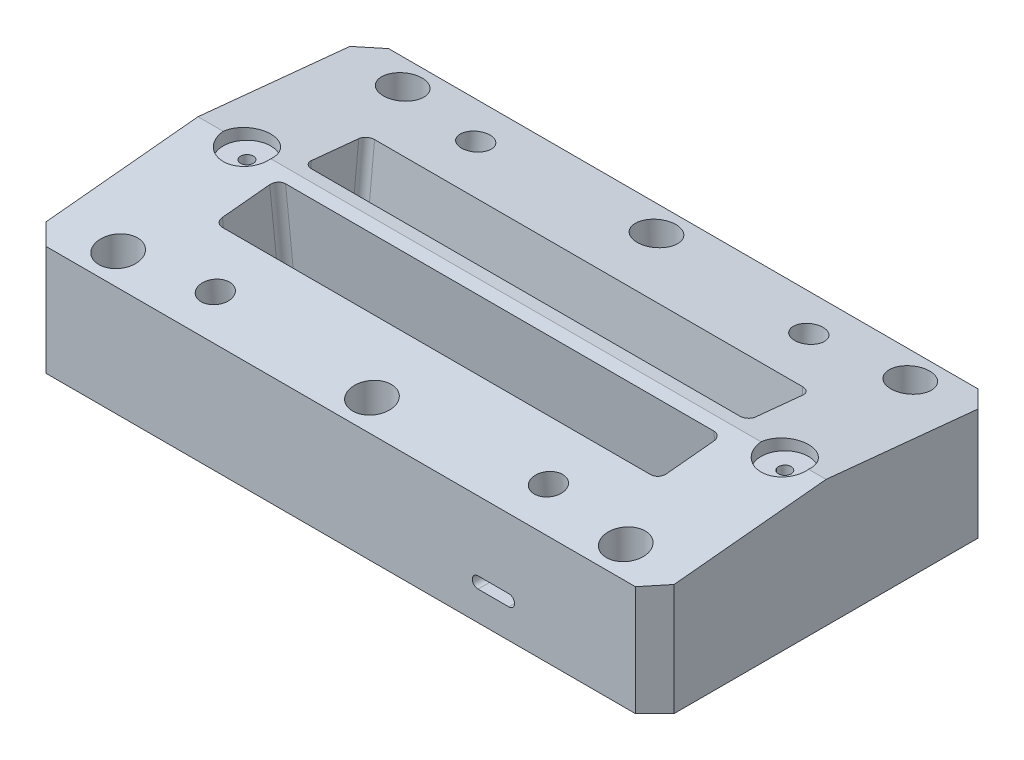
SolidWorks part; units mm, degrees
material "Custom Plastic"
ref_plane "Front Plane" through (0, 0, 0) normal (0, 0, 1) x (1, 0, 0)
ref_plane "Top Plane" through (0, 0, 0) normal (0, 1, 0) x (1, 0, 0)
ref_plane "Right Plane" through (0, 0, 0) normal (1, 0, 0) x (0, 0, -1)
sketch "Sketch1" plane through (0, 0, 0) normal (0, 1, 0) x (1, 0, 0)
  line L1 (0, 0) -> (198, 0)
  line L2 (0, 0) -> (0, 108)
  line L3 (0, 108) -> (198, 108)
  line L4 (198, 0) -> (198, 108)
  dimension "D1" = 198
  dimension "D2" = 108
extrude "Boss-Extrude1" add sketch "Sketch1" along normal blind 40
ref_plane "Left" through (198, 0, 0) normal (1, 0, 0) x (0, 0, -1)
ref_plane "Bot" through (0, 40, 0) normal (0, 1, 0) x (1, 0, 0)
ref_plane "der loco" through (0, 0, -52) normal (0, 0, -1) x (-1, 0, 0)
sketch "Sketch4" plane through (0, 0, 0) normal (0, 1, 0) x (1, 0, 0)
  line L0 (0, 108) -> (0, 0) construction
  line L1 (8.5, 31.5) -> (189.5, 31.5)
  line L2 (8.5, 31.5) -> (8.5, 76.5)
  line L3 (8.5, 76.5) -> (189.5, 76.5)
  line L4 (189.5, 31.5) -> (189.5, 76.5)
  line L5 (0, 0) -> (198, 0) construction
  dimension "D1" = 181
  dimension "D2" = 8.5
  dimension "D3" = 45
  dimension "D4" = 31.5
extrude "Cut-Extrude2" cut sketch "Sketch4" along normal blind 10 contours L2 L1 L4 L3
ref_plane "Plane32" through (0, 10, 0) normal (0, -1, 0) x (-1, 0, 0)
sketch "Sketch5" plane through (198, 0, 0) normal (1, 0, 0) x (0, 0, -1)
  line L0 (54, 40) -> (108, 34.6577)
  line L1 (0, 40) -> (108, 40) construction
  line L2 (108, 34.6577) -> (108, 40)
  line L3 (108, 40) -> (54, 40)
  line L4 (108, 40) -> (108, 0) construction
  dimension "D1" = 5.65
  dimension "D2" = 54
extrude "Cut-Extrude3" cut sketch "Sketch5" against normal up to vertex (198 mm away) up to point (0, 40, 0)
ref_plane "Plane24" through (0, 10, 0) normal (0, -1, 0) x (-1, 0, 0)
sketch "Sketch53" plane through (0, 10, 0) normal (0, -1, 0) x (-1, 0, 0)
  line L0 (-8.5, 51.5) -> (-8.5, 31.5)
  line L1 (-8.5, 76.5) -> (-8.5, 31.5) construction
  line L2 (-8.5, 31.5) -> (-39.5, 31.5)
  line L3 (-8.5, 31.5) -> (-189.5, 31.5) construction
  line L4 (-39.5, 31.5) -> (-8.5, 51.5)
  line L5 (-8.5, 54) -> (-189.5, 54) construction
  line L6 (-189.5, 31.5) -> (-189.5, 76.5) construction
  line L7 (-8.5, 56.5) -> (-8.5, 76.5)
  line L8 (-8.5, 76.5) -> (-39.5, 76.5)
  line L9 (-39.5, 76.5) -> (-8.5, 56.5)
  line L10 (-99, 76.5) -> (-99, 31.5) construction
  line L11 (-8.5, 76.5) -> (-189.5, 76.5) construction
  line L12 (-8.5, 31.5) -> (-189.5, 31.5) construction
  line L13 (-158.5, 76.5) -> (-189.5, 56.5)
  line L14 (-189.5, 76.5) -> (-158.5, 76.5)
  line L15 (-189.5, 56.5) -> (-189.5, 76.5)
  line L16 (-158.5, 31.5) -> (-189.5, 51.5)
  line L17 (-189.5, 31.5) -> (-158.5, 31.5)
  line L18 (-189.5, 51.5) -> (-189.5, 31.5)
  dimension "D1" = 31
  dimension "D2" = 20
extrude "Boss-Extrude11" add sketch "Sketch53" along normal up to surface (10 mm away) up to face at (99, 0, -54)
ref_plane "izq loco" through (0, 0, -57) normal (0, 0, -1) x (-1, 0, 0)
sketch "Sketch18" plane through (198, 0, 0) normal (1, 0, 0) x (0, 0, -1)
  line L0 (0, 34.6577) -> (0, 40)
  line L1 (0, 40) -> (0, 0) construction
  line L2 (0, 40) -> (54, 40)
  line L3 (54, 40) -> (0, 34.6577)
  line L4 (0, 40) -> (54, 40) construction
  dimension "D1" = 54
  dimension "D2" = 5.65
extrude "Cut-Extrude12" cut sketch "Sketch18" against normal up to surface (198 mm away) up to face at (0, 22.9315, -54)
sketch "Sketch60" plane through (0, 0, 0) normal (0, 1, 0) x (1, 0, 0)
  point P0 (8.5, 31.5)
  point P1 (39.5, 31.5)
  point P2 (8.5, 76.5)
  point P6 (39.5, 76.5)
  dimension "D1" = 20
  dimension "D2" = 31
  dimension "D3" = 20
  dimension "D4" = 31
ref_axis "Axis6" through (8.5, 0, -31.5) along (1, 0, 0)
sketch "Sketch69" plane through (0, 10, 0) normal (0, -1, 0) x (-1, 0, 0)
  point P0 (-39.5, 56.5)
  point P1 (-8.5, 51.5)
  point P2 (-38.5, 51.5)
  point P3 (-8.5, 56.5)
  dimension "D1" = 31
  dimension "D2" = 20
  dimension "D3" = 20
  dimension "D4" = 30
sketch "der loco axis" plane through (0, 0, -52) normal (0, 0, -1) x (-1, 0, 0)
  point P0 (-8.5, 8.5)
  point P1 (-38.5, 8.5)
  dimension "D1" = 1.5
sketch "izq loco axis" plane through (0, 0, -57) normal (0, 0, -1) x (-1, 0, 0)
  line L0 (-39.5, 0) -> (-39.5, 10) construction
  line L1 (-8.5, 0) -> (-8.5, 10) construction
  point P0 (-8.5, 8.4959)
  point P1 (-39.5, 8.4959)
  dimension "D1" = 1.5041
ref_plane "Plane3" through (0, 44.9028, -4.4423) normal (0, 0.9951, -0.0985) x (1, 0, 0)
ref_axis "Axis8" through (39.5, 0, -76.5) along (-1, 0, 0)
ref_axis "Axis9" through (8.5, 8.4959, -57) along (1, 0, 0)
ref_axis "Axis10" through (38.5, 8.5, -52) along (-1, 0, 0)
ref_plane "Izq bueno" through (0, 28.0127, -12.2048) normal (0, 0.9168, -0.3994) x (1, 0, 0)
sketch "Izq" plane through (0, 28.0127, -12.2048) normal (0, 0.9168, -0.3994) x (1, 0, 0)
  line L0 (8.5, 48.8622) -> (29.5, 70.1326)
  line L1 (29.5, 70.1326) -> (8.5, 70.1326)
  line L2 (8.5, 70.1326) -> (8.5, 48.8622)
  dimension "D1" = 21
extrude "Cut-Extrude28" cut sketch "Izq" against normal blind 14.5
ref_plane "Der bueno" through (0, -11.1449, -4.6211) normal (0, 0.9237, 0.383) x (1, 0, 0)
sketch "Der" plane through (0, -11.1449, -4.6211) normal (0, 0.9237, 0.383) x (1, 0, 0)
  line L0 (8.5, 51.2902) -> (29.5, 29.0979)
  line L1 (29.5, 29.0979) -> (8.5, 29.0979)
  line L2 (8.5, 29.0979) -> (8.5, 51.2902)
  dimension "D1" = 21
extrude "Cut-Extrude29" cut sketch "Der" against normal blind 14.5
sketch "Sketch97" plane through (0, 0, 0) normal (0, 1, 0) x (1, 0, 0)
  line L0 (8.5, 57.5) -> (29.5, 76.5)
  line L1 (29.5, 76.5) -> (158.5, 76.5)
  line L3 (158.5, 31.5) -> (29.5, 31.5)
  line L4 (29.5, 31.5) -> (8.5, 51.5)
  line L5 (8.5, 51.5) -> (8.5, 57.5)
  line L7 (158.5, 76.5) -> (189.5, 56.5)
  line L8 (189.5, 56.5) -> (189.5, 51.5)
  line L9 (189.5, 51.5) -> (158.5, 31.5)
  line L10 (39.5, 76.5) -> (158.5, 76.5) construction
  dimension "D1" = 6
extrude "Cut-Extrude40" cut sketch "Sketch97" along normal up to surface (10 mm away) up to face at (99, 10, -54)
ref_axis "Axis11" through (99, 0, -108) along (0, 0, 1)
ref_plane "Plane33" through (99, 0, 0) normal (1, 0, 0) x (0, 0, -1)
mirror "Mirror2" about plane through (99, 0, 0) normal (1, 0, 0) of "Cut-Extrude29", "Cut-Extrude40", "Cut-Extrude28"
sketch "Sketch6" plane through (0, 44.9028, -4.4423) normal (0, 0.9951, -0.0985) x (1, 0, 0)
  line L0 (0, 49.7996) -> (198, 49.7996) construction
  line L1 (28.9, 77.1996) -> (169.5, 77.1996)
  line L2 (25.9, 74.1996) -> (25.9, 53.5996)
  line L3 (28.9, 50.5996) -> (169.5, 50.5996)
  line L4 (172.5, 74.1996) -> (172.5, 53.5996)
  line L7 (28.6, 53.2996) -> (169.8, 53.2996)
  line L8 (28.6, 53.2996) -> (28.6, 74.4996)
  line L9 (28.6, 74.4996) -> (169.8, 74.4996)
  line L10 (169.8, 53.2996) -> (169.8, 74.4996)
  line L13 (198, 49.7996) -> (198, 104.0632) construction
  arc A0 (169.5, 77.1996) -> (172.5, 74.1996) centre (169.5, 74.1996) cw
  arc A1 (169.5, 50.5996) -> (172.5, 53.5996) centre (169.5, 53.5996) ccw
  arc A2 (25.9, 53.5996) -> (28.9, 50.5996) centre (28.9, 53.5996) ccw
  arc A3 (28.9, 77.1996) -> (25.9, 74.1996) centre (28.9, 74.1996) ccw
  dimension "D1" = 3
  dimension "D2" = 146.6
  dimension "D3" = 20.6
  dimension "D4" = 25.5
  dimension "D5" = 3.5
  dimension "D6" = 2.7
  dimension "D7" = 2.7
  dimension "D8" = 2.7
  dimension "D9" = 2.7
sketch "Sketch9" plane through (0, 40, 0) normal (0, 1, 0) x (1, 0, 0)
  line L1 (0, 54) -> (198, 54) construction
  circle A0 centre (15.45, 54) radius 8
  point P2 (0, 0)
  point P3 (15.45, 54)
  dimension "D1" = 16
  dimension "D2" = 15.45
sketch "Sketch12" plane through (0, 40, 0) normal (0, 1, 0) x (1, 0, 0)
  line L1 (0, 108) -> (198, 108) construction
  line L4 (0, 0) -> (198, 0) construction
  circle A0 centre (19.7, 98.85) radius 3.15
  circle A1 centre (99.7, 9.15) radius 3.15
  circle A2 centre (179.7, 9.15) radius 3.15
  circle A3 centre (19.7, 9.15) radius 3.15
  circle A4 centre (99.7, 98.85) radius 3.15
  circle A5 centre (179.7, 98.85) radius 3.15
  dimension "D1" = 9.15
  dimension "D2" = 6.3
  dimension "D3" = 9.15
  dimension "D4" = 19.7
  dimension "D7" = 80
  dimension "D9" = 80
extrude "Cut-Extrude9" cut sketch "Sketch12" against normal through all
sketch "Sketch13" plane through (0, 44.9028, -4.4423) normal (0, 0.9951, -0.0985) x (1, 0, 0)
  line L1 (0, 104.0632) -> (198, 104.0632) construction
  line L2 (198, 49.7996) -> (198, 104.0632) construction
  line L3 (0, 49.7996) -> (0, 104.0632) construction
  circle A0 centre (46.5, 91.0632) radius 4.5
  circle A1 centre (151.5, 91.0632) radius 4.5
  dimension "D1" = 9
  dimension "D4" = 9
  dimension "D2" = 46.5
  dimension "D3" = 13
  dimension "D5" = 46.5
extrude "Cut-Extrude10" cut sketch "Sketch13" against normal blind 16.5
sketch "Sketch14" plane through (0, 34.0326, 6.3177) normal (0, 0.9951, 0.0985) x (1, 0, 0)
  line L3 (198, 6.3486) -> (198, 60.6122) construction
  line L4 (0, 60.6122) -> (198, 60.6122) construction
  circle A0 centre (46.5, 19.3937) radius 4.5
  circle A1 centre (151.5, 19.3937) radius 4.5
  dimension "D1" = 9
  dimension "D2" = 9
  dimension "D3" = 46.5
  dimension "D4" = 41.2185
  dimension "D5" = 46.5
extrude "Cut-Extrude11" cut sketch "Sketch14" against normal blind 16.5
ref_plane "Plane9" through (0, 34.3217, 3.3955) normal (0, 0.9951, 0.0985) x (1, 0, 0)
sketch "Sketch23" plane through (0, 34.3217, 3.3955) normal (0, 0.9951, 0.0985) x (1, 0, 0)
  line L0 (0, 57.6757) -> (198, 57.6757) construction
  line L1 (28.9, 56.8757) -> (169.5, 56.8757)
  line L2 (25.9, 53.8757) -> (25.9, 33.2757)
  line L3 (28.9, 30.2757) -> (169.5, 30.2757)
  line L4 (172.5, 53.8757) -> (172.5, 33.2757)
  line L7 (28.6, 54.1757) -> (169.8, 54.1757)
  line L8 (28.6, 54.1757) -> (28.6, 32.9757)
  line L9 (28.6, 32.9757) -> (169.8, 32.9757)
  line L10 (169.8, 54.1757) -> (169.8, 32.9757)
  line L12 (198, 3.4121) -> (198, 57.6757) construction
  arc A0 (169.5, 56.8757) -> (172.5, 53.8757) centre (169.5, 53.8757) cw
  arc A1 (169.5, 30.2757) -> (172.5, 33.2757) centre (169.5, 33.2757) ccw
  arc A2 (25.9, 33.2757) -> (28.9, 30.2757) centre (28.9, 33.2757) ccw
  arc A3 (28.9, 56.8757) -> (25.9, 53.8757) centre (28.9, 53.8757) ccw
  point P10 (172.5, 56.8757)
  point P15 (25.9, 30.2757)
  point P18 (25.9, 56.8757)
  dimension "D5" = 3
  dimension "D1" = 146.6
  dimension "D2" = 20.6
  dimension "D3" = 3.5
  dimension "D4" = 25.5
  dimension "D6" = 2.7
  dimension "D7" = 2.7
  dimension "D8" = 2.7
  dimension "D9" = 2.7
sketch "Sketch41" plane through (0, 0, 0) normal (0, 1, 0) x (1, 0, 0)
  line L0 (198, 0) -> (198, 108) construction
  line L1 (198, 108) -> (0, 108) construction
  line L2 (0, 0) -> (198, 0) construction
  circle A0 centre (139.5, 9) radius 2.9
  circle A1 centre (139.5, 99) radius 2.9
  dimension "D1" = 5.8
  dimension "D4" = 5.8
  dimension "D2" = 58.5
  dimension "D3" = 58.5
  dimension "D5" = 9
  dimension "D6" = 9
extrude "Cut-Extrude21" cut sketch "Sketch41" along normal blind 7
sketch "Sketch42" plane through (0, 0, 0) normal (0, 0, 1) x (1, 0, 0)
  line L0 (198, 34.6577) -> (198, 0) construction
  line L5 (0, 0) -> (198, 0) construction
  line L6 (142.3, 12.8) -> (152, 12.8)
  line L7 (142.3, 9.2) -> (152, 9.2)
  arc A0 (142.3, 12.8) -> (142.3, 9.2) centre (142.3, 11) ccw
  arc A2 (152, 12.8) -> (152, 9.2) centre (152, 11) cw
  dimension "D2" = 1.8
  dimension "D3" = 1.8
  dimension "D1" = 9.7
  dimension "D5" = 46
  dimension "D6" = 11
extrude "Cut-Extrude22" cut sketch "Sketch42" against normal blind 10
ref_plane "Plane19" through (0, 0, -108) normal (0, 0, -1) x (-1, 0, 0)
sketch "Sketch43" plane through (0, 0, -108) normal (0, 0, -1) x (-1, 0, 0)
  line L0 (-55.7, 11) -> (-46, 11) construction
  line L1 (-55.7, 12.8) -> (-46, 12.8)
  line L2 (-55.7, 9.2) -> (-46, 9.2)
  line L3 (-198, 0) -> (0, 0) construction
  line L4 (0, 34.6577) -> (0, 0) construction
  arc A0 (-55.7, 12.8) -> (-55.7, 9.2) centre (-55.7, 11) ccw
  arc A1 (-46, 9.2) -> (-46, 12.8) centre (-46, 11) ccw
  point P2 (-50.85, 11)
  dimension "D2" = 1.8
  dimension "D1" = 9.7
  dimension "D3" = 11
  dimension "D4" = 46
extrude "Cut-Extrude23" cut sketch "Sketch43" against normal blind 10
sketch "Sketch84" plane through (0, 44.9028, -4.4423) normal (0, 0.9951, -0.0985) x (1, 0, 0)
  line L0 (0, 49.7996) -> (198, 49.7996) construction
  line L1 (31.7, 53.8996) -> (166.7, 53.8996)
  line L2 (29.2, 56.3996) -> (29.2, 71.3996)
  line L3 (31.7, 73.8996) -> (166.7, 73.8996)
  line L4 (169.2, 56.3996) -> (169.2, 71.3996)
  line L7 (0, 49.7996) -> (0, 104.0632) construction
  arc A0 (166.7, 53.8996) -> (169.2, 56.3996) centre (166.7, 56.3996) ccw
  arc A1 (166.7, 73.8996) -> (169.2, 71.3996) centre (166.7, 71.3996) cw
  arc A2 (29.2, 71.3996) -> (31.7, 73.8996) centre (31.7, 71.3996) cw
  arc A3 (31.7, 53.8996) -> (29.2, 56.3996) centre (31.7, 56.3996) cw
  point P10 (169.2, 53.8996)
  point P13 (169.2, 73.8996)
  point P16 (29.2, 73.8996)
  point P19 (169.2, 63.8996)
  dimension "D5" = 2.5
  dimension "D1" = 140
  dimension "D2" = 20
  dimension "D3" = 4.1
  dimension "D4" = 29.2
extrude "Cut-Extrude35" cut sketch "Sketch84" against normal blind 55.4
sketch "Sketch83" plane through (0, 34.3217, 3.3955) normal (0, 0.9951, 0.0985) x (1, 0, 0)
  line L1 (31.7, 53.5757) -> (166.7, 53.5757)
  line L2 (29.2, 51.0757) -> (29.2, 36.0757)
  line L3 (31.7, 33.5757) -> (166.7, 33.5757)
  line L4 (169.2, 51.0757) -> (169.2, 36.0757)
  line L7 (0, 57.6757) -> (198, 57.6757) construction
  line L8 (0, 57.6757) -> (0, 3.4121) construction
  arc A0 (166.7, 33.5757) -> (169.2, 36.0757) centre (166.7, 36.0757) ccw
  arc A1 (166.7, 53.5757) -> (169.2, 51.0757) centre (166.7, 51.0757) cw
  arc A2 (29.2, 36.0757) -> (31.7, 33.5757) centre (31.7, 36.0757) ccw
  arc A3 (31.7, 53.5757) -> (29.2, 51.0757) centre (31.7, 51.0757) ccw
  point P12 (169.2, 53.5757)
  point P15 (29.2, 33.5757)
  point P18 (29.2, 53.5757)
  point P19 (169.2, 43.5757)
  dimension "D5" = 2.5
  dimension "D1" = 140
  dimension "D2" = 20
  dimension "D3" = 29.2
  dimension "D4" = 4.1
extrude "Cut-Extrude34" cut sketch "Sketch83" against normal blind 55.4
sketch "Sketch85" plane through (0, 40, 0) normal (0, 1, 0) x (1, 0, 0)
  line L0 (0, 101.9) -> (6.1, 108)
  line L3 (6.1, 108) -> (0, 108)
  line L4 (0, 108) -> (0, 101.9)
  line L5 (0, 0) -> (6.1, 0)
  line L7 (6.1, 0) -> (0, 6.1)
  line L9 (0, 6.1) -> (0, 0)
  line L10 (198, 6.1) -> (191.9, 0)
  line L11 (198, 0) -> (198, 54) construction
  line L12 (0, 0) -> (198, 0) construction
  line L13 (191.9, 0) -> (198, 0)
  line L14 (198, 0) -> (198, 6.1)
  line L15 (198, 108) -> (191.9, 108)
  line L16 (0, 108) -> (198, 108) construction
  line L17 (191.9, 108) -> (198, 101.9)
  line L18 (198, 54) -> (198, 108) construction
  line L19 (198, 101.9) -> (198, 108)
  line L20 (0, 54) -> (0, 108) construction
  line L21 (0, 108) -> (198, 108) construction
  line L22 (0, 0) -> (198, 0) construction
  line L23 (0, 54) -> (0, 0) construction
  point P2 (0, 0)
  point P3 (0, 0)
  point P4 (0, 0)
  point P15 (0, 0)
  point P28 (0, 0)
  point P36 (0, 0)
  dimension "D1" = 6.1
  dimension "D2" = 6.1
  dimension "D3" = 6.1
  dimension "D4" = 6.1
  dimension "D5" = 6.1
  dimension "D6" = 6.1
  dimension "D7" = 6.1
extrude "Cut-Extrude36" cut sketch "Sketch85" against normal blind 55.4
sketch "Sketch90" plane through (0, 40, 0) normal (0, 1, 0) x (1, 0, 0)
  circle A0 centre (19.7, 9.15) radius 6.1
  circle A1 centre (99.7, 9.15) radius 6.1
  circle A2 centre (179.7, 9.15) radius 6.1
  circle A3 centre (99.7, 98.85) radius 6.1
  circle A4 centre (179.7, 98.85) radius 6.1
  circle A5 centre (19.7, 98.85) radius 6.1
  circle A6 centre (179.7, 98.85) radius 3.15 construction
  circle A7 centre (99.7, 98.85) radius 3.15 construction
  dimension "D1" = 12.2
  dimension "D2" = 3
  dimension "D3" = 2
extrude "Cut-Extrude38" cut sketch "Sketch90" against normal blind 17
sketch "Sketch96" plane through (0, 0, 0) normal (0, 1, 0) x (1, 0, 0)
  line L0 (0, 54) -> (198, 54) construction
  line L1 (198, 6.1) -> (198, 101.9) construction
  circle A0 centre (15.45, 54) radius 2
  circle A1 centre (185, 54) radius 2
  dimension "D1" = 4
  dimension "D2" = 4
  dimension "D3" = 13
extrude "Cut-Extrude39" cut sketch "Sketch96" along normal through all
sketch "Sketch98" plane through (0, 40, 0) normal (0, 1, 0) x (1, 0, 0)
  circle A0 centre (185, 54) radius 7.5
  circle A1 centre (15.45, 54) radius 7.5
  dimension "D1" = 15
  dimension "D2" = 15
extrude "Cut-Extrude41" cut sketch "Sketch98" against normal blind 4
sketch "Sketch99" plane through (198, 0, 0) normal (1, 0, 0) x (0, 0, -1)
  line L0 (57.483, 39.6554) -> (78.58, 37.5683) construction
  line L1 (54, -103.26) -> (68.0315, 38.6118) construction
  line L2 (54, -103.26) -> (142.4681, -112.0123) construction
  line L3 (54, 40) -> (101.9, 35.2612) construction
  line L4 (54, -103.26) -> (-34.4681, -112.0123) construction
  line L5 (6.1, 35.2612) -> (54, 40) construction
  line L6 (54.0042, -103.26) -> (39.9685, 38.6118) construction
  line L7 (-34.9, -103.26) -> (142.9, -103.26) construction
  line L8 (54, -103.26) -> (39.9685, 38.6118) construction
  line L9 (32.5049, 37.8735) -> (47.4321, 39.3502) construction
  line L10 (53.9958, -103.26) -> (68.0315, 38.6118) construction
  circle A0 centre (54, -103.26) radius 88.9
  point P19 (39.9685, 38.6118)
  dimension "D1" = 177.8
  dimension "D2" = 103.26
  dimension "D3" = 90.002
  dimension "D4" = 90.002
  dimension "D5" = 0.0042
